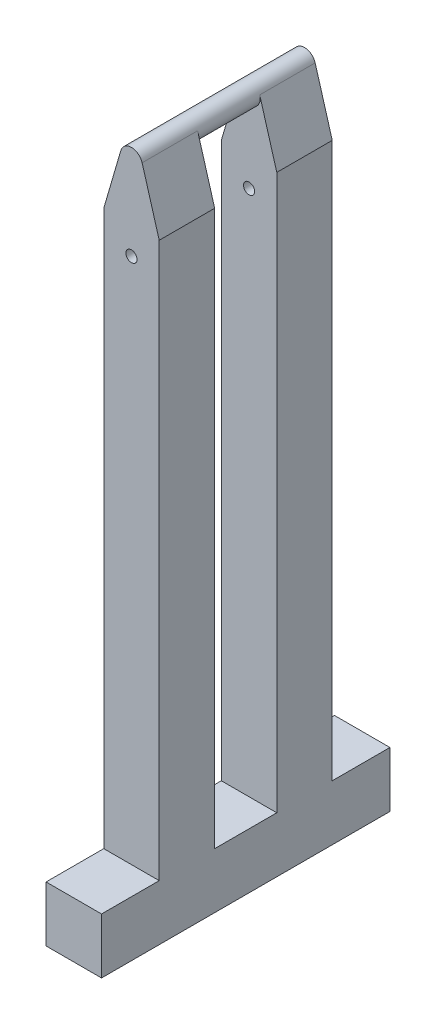
SolidWorks part; units mm, degrees
ref_plane "Front Plane" through (0, 0, 0) normal (0, 0, 1) x (1, 0, 0)
ref_plane "Top Plane" through (0, 0, 0) normal (0, 1, 0) x (1, 0, 0)
ref_plane "Right Plane" through (0, 0, 0) normal (1, 0, 0) x (0, 0, -1)
sketch "Sketch1" plane through (0, 0, 0) normal (0, 1, 0) x (1, 0, 0)
  line L0 (-1000, 0) -> (49000, 0) construction
  line L1 (-12.5, 39) -> (12.5, 39)
  line L2 (-12.5, 39) -> (-12.5, 14)
  line L3 (-12.5, 14) -> (12.5, 14)
  line L4 (12.5, 39) -> (12.5, 14)
  line L5 (-12.5, 39) -> (12.5, 14) construction
  line L6 (-12.5, 14) -> (12.5, 39) construction
  line L7 (-12.5, -14) -> (12.5, -39) construction
  line L8 (-12.5, -39) -> (12.5, -14) construction
  line L9 (12.5, -39) -> (12.5, -14)
  line L10 (-12.5, -14) -> (12.5, -14)
  line L11 (-12.5, -39) -> (-12.5, -14)
  line L12 (-12.5, -39) -> (12.5, -39)
  point P0 (0, 26.5)
  point P12 (0, -26.5)
  dimension "D1" = 25
  dimension "D2" = 25
  dimension "D3" = 14
extrude "Boss-Extrude1" add sketch "Sketch1" along normal blind 250
sketch "Sketch2" plane through (0, 0, 39) normal (0, 0, 1) x (1, 0, 0)
  line L0 (-12.5, 250) -> (12.5, 250) construction
  line L1 (-12.5, 225) -> (12.5, 225) construction
  line L2 (-12.5, 225) -> (-12.5, 250) construction
  line L3 (-12.5, 250) -> (12.5, 250) construction
  line L4 (12.5, 225) -> (12.5, 250) construction
  line L5 (-12.5, 225) -> (12.5, 250) construction
  line L6 (-12.5, 250) -> (12.5, 225) construction
  line L7 (12.5, 250) -> (12.5, 0) construction
  line L8 (-12.5, 250) -> (-12.5, 0) construction
  circle A0 centre (0, 237.5) radius 2.5
  point P0 (0, 237.5)
  dimension "D2" = 5
  dimension "D1" = 25
extrude "Cut-Extrude1" cut sketch "Sketch2" against normal through all
sketch "Sketch3" plane through (0, 0, 39) normal (0, 0, 1) x (1, 0, 0)
  line L0 (-12.5, 250) -> (-4.8, 276.4)
  line L1 (4.8, 276.4) -> (12.5, 250)
  line L2 (-12.5, 250) -> (12.5, 250) construction
  line L3 (-12.5, 250) -> (12.5, 250)
  arc A0 (4.8, 276.4) -> (-4.8, 276.4) centre (0, 275) ccw
  dimension "D1" = 10
  dimension "D2" = 25
extrude "Boss-Extrude2" add sketch "Sketch3" against normal up to surface (78 mm away) up to face at (2.5, 237.5, -39)
sketch "Sketch4" plane through (0, 250, 0) normal (0, -1, 0) x (1, 0, 0)
  line L1 (-12.5, 14) -> (12.5, 14)
  line L2 (-12.5, 14) -> (-12.5, -14)
  line L3 (-12.5, -14) -> (12.5, -14)
  line L4 (12.5, 14) -> (12.5, -14)
extrude "Cut-Extrude2" cut sketch "Sketch4" against normal through all
sketch "Sketch5" plane through (0, 0, -39) normal (0, 0, -1) x (-1, 0, 0)
  circle A1 centre (0, 275) radius 5
  dimension "D1" = 10
extrude "Boss-Extrude3" add sketch "Sketch5" against normal up to surface (78 mm away) up to face at (0, 176.0667, 39)
sketch "Sketch6" plane through (0, 0, 0) normal (0, -1, 0) x (1, 0, 0)
  line L1 (-12.5, -65) -> (12.5, -65)
  line L2 (-12.5, -65) -> (-12.5, 65)
  line L3 (-12.5, 65) -> (12.5, 65)
  line L4 (12.5, -65) -> (12.5, 65)
  line L5 (-12.5, -65) -> (12.5, 65) construction
  line L6 (-12.5, 65) -> (12.5, -65) construction
  point P0 (0, 0)
  dimension "D1" = 25
  dimension "D2" = 130
extrude "Boss-Extrude4" add sketch "Sketch6" along normal blind 25
